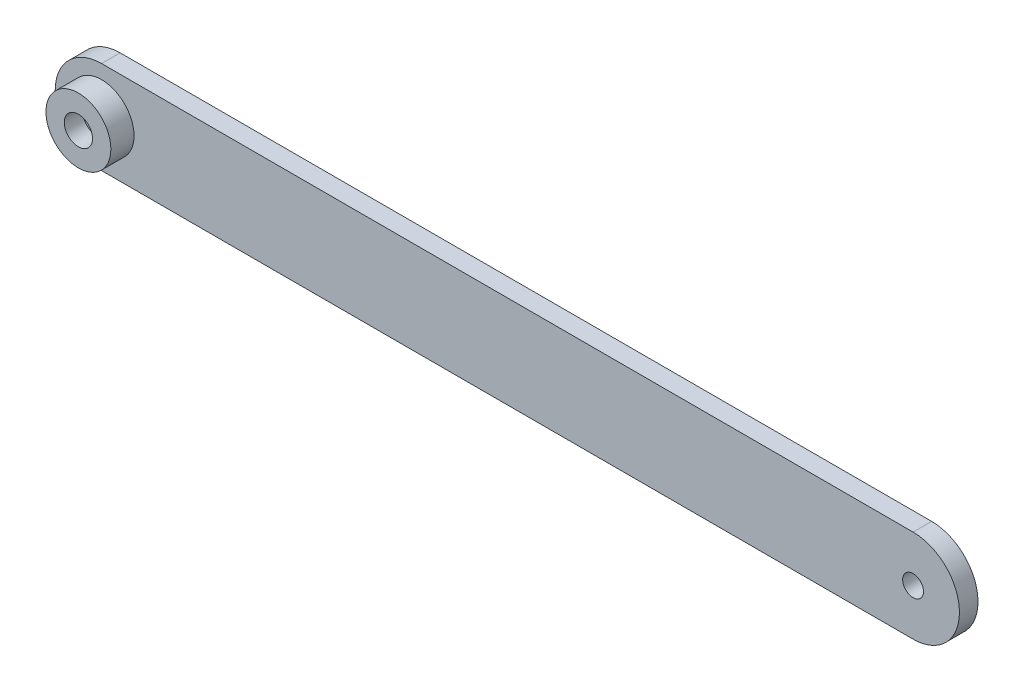
SolidWorks part; units mm, degrees
ref_plane "Front Plane" through (0, 0, 0) normal (0, 0, 1) x (1, 0, 0)
ref_plane "Top Plane" through (0, 0, 0) normal (0, 1, 0) x (1, 0, 0)
ref_plane "Right Plane" through (0, 0, 0) normal (1, 0, 0) x (0, 0, -1)
sketch "Sketch1" plane through (0, 0, 0) normal (0, 0, 1) x (1, 0, 0)
  line L0 (0, 0) -> (175, 0) construction
  line L1 (0, 10) -> (175, 10)
  line L2 (0, -10) -> (175, -10)
  arc A0 (0, 10) -> (0, -10) centre (0, 0) ccw
  arc A1 (175, -10) -> (175, 10) centre (175, 0) ccw
  circle A3 centre (175, 0) radius 2.25
  circle A9 centre (0, 0) radius 1
  point P3 (87.5, 0)
  dimension "D1" = 10
  dimension "D3" = 4.5
  dimension "D4" = 2
  dimension "D2" = 175
extrude "Boss-Extrude1" add sketch "Sketch1" along normal mid plane 4
sketch "Sketch2" plane through (0, 0, -2) normal (0, 0, -1) x (-1, 0, 0)
  circle A0 centre (0, 0) radius 2.5
  dimension "D1" = 5
extrude "Cut-Extrude1" cut sketch "Sketch2" against normal blind 3
sketch "Sketch4" plane through (0, 0, 2) normal (0, 0, 1) x (1, 0, 0)
  circle A0 centre (0, 0) radius 7
  circle A1 centre (0, 0) radius 1 construction
  circle A2 centre (0, 0) radius 1
  dimension "D1" = 14
extrude "Boss-Extrude2" add sketch "Sketch4" along normal blind 1
sketch "Sketch5" plane through (0, 0, 3) normal (0, 0, 1) x (1, 0, 0)
  circle A0 centre (0, 0) radius 7 construction
  circle A1 centre (0, 0) radius 7
  circle A2 centre (0, 0) radius 3.05
  dimension "D1" = 6.1
extrude "Boss-Extrude3" add sketch "Sketch5" along normal blind 4
sketch "Sketch6" plane through (0, 0, -2) normal (0, 0, -1) x (-1, 0, 0)
  line L0 (0, 0) -> (2.5, 0) construction
  line L1 (0, 0) -> (2.4721, 0.3726) construction
  line L2 (2.4721, 0.3726) -> (2.15, 0)
  line L3 (2.15, 0) -> (2.4721, -0.3726)
  circle A0 centre (0, 0) radius 2.5 construction
  arc A1 (2.4721, -0.3726) -> (2.4721, 0.3726) centre (0, 0) ccw
  point P2 (0, 0)
  point P4 (2.15, 0)
  dimension "D1" = 0.35
  dimension "D2" = 8.571
extrude "Boss-Extrude4" add sketch "Sketch6" against normal blind 3.2
pattern_circular "CirPattern2" count 21 over 360 about axis through (0, 0, 1) along (0, 0, -1) of "Boss-Extrude4" reverse direction yes
